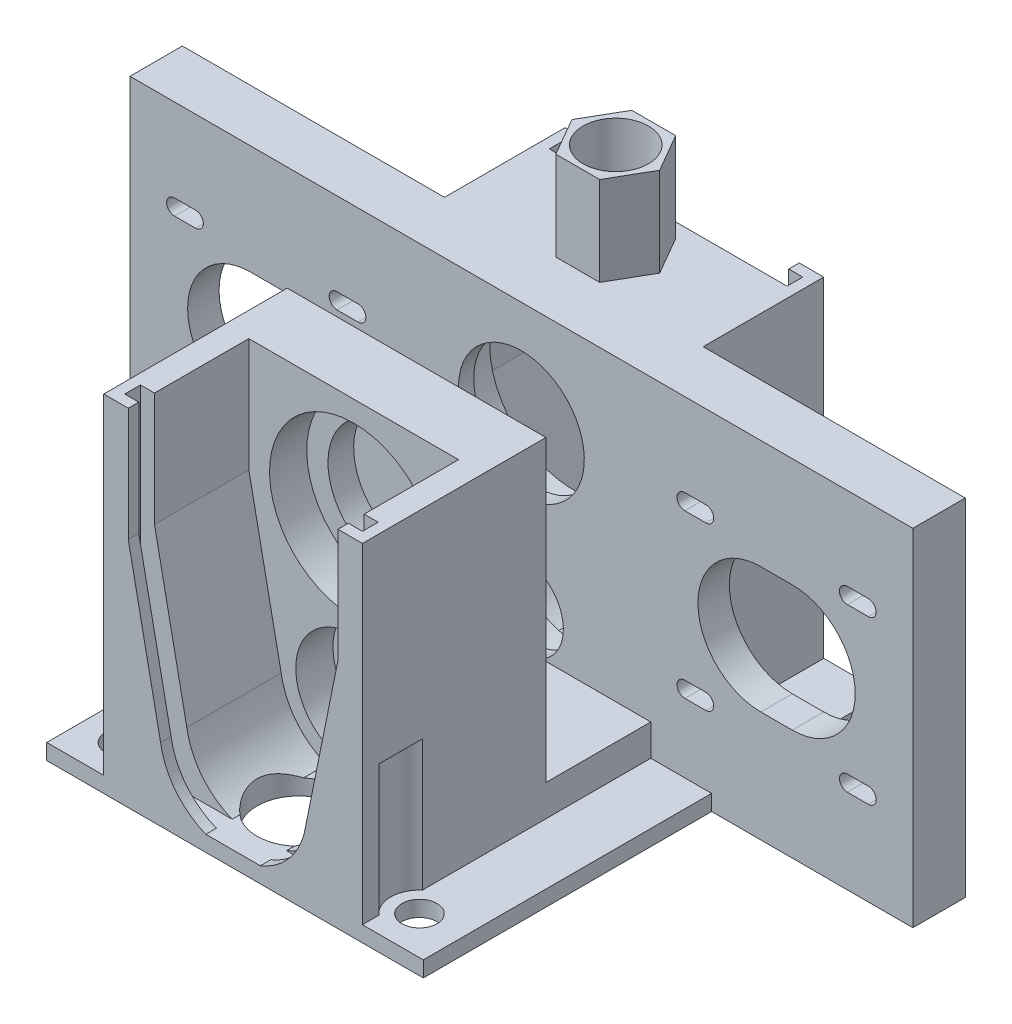
SolidWorks part; units mm, degrees
ref_plane "Front Plane" through (0, 0, 0) normal (0, 0, 1) x (1, 0, 0)
ref_plane "Top Plane" through (0, 0, 0) normal (0, 1, 0) x (1, 0, 0)
ref_plane "Right Plane" through (0, 0, 0) normal (1, 0, 0) x (0, 0, -1)
ref_axis "Axis1" through (88.99, 0, 0) along (-1, 0, 0)
ref_plane "Plane1" through (0, 0, 0) normal (0, 0, -1) x (-1, 0, 0)
ref_plane "Plane2" through (0, 0, 0) normal (0, -1, 0) x (-1, 0, 0)
ref_plane "Plane3" through (0, 0, -42) normal (0, 0, -1) x (-1, 0, 0)
sketch "Sketch2" plane through (0, 0, 0) normal (0, 0, -1) x (-1, 0, 0)
  line L2 (0, 58.0413) -> (0, 28.0413) construction
  line L3 (-24.6785, 78.0413) -> (24.6785, 78.0413)
  line L4 (57.5751, 12.0413) -> (-72.0682, 12.0413) construction
  line L5 (-24.6785, 78.0413) -> (-24.6785, 12.0413)
  line L6 (-24.6785, 12.0413) -> (24.6785, 12.0413)
  line L7 (24.6785, 12.0413) -> (24.6785, 78.0413)
  circle A0 centre (0, 28.0413) radius 11 construction
  circle A1 centre (0, 58.0413) radius 16 construction
  point P4 (0, 58.0413)
  point P6 (0, 28.0413)
  point P7 (20.0824, 64.1811)
  point P8 (15.3009, 32.7193)
  dimension "D1" = 32
  dimension "D2" = 22
  dimension "D6" = 66
  dimension "D3" = 30
  dimension "D5" = 20
  dimension "D4" = 16
extrude "Boss-Extrude1" add sketch "Sketch2" along normal blind 65
ref_plane "Plane5" through (0, 12.0413, 0) normal (0, -1, 0) x (-1, 0, 0)
sketch "Sketch3" plane through (0, 0, 0) normal (0, 0, -1) x (-1, 0, 0)
  line L0 (-24.6785, 12.0413) -> (24.6785, 12.0413) construction
  line L1 (0, 0) -> (0, 102.6324) construction
  circle A0 centre (0, 28.0413) radius 8
  circle A1 centre (0, 58.0413) radius 12
  circle A3 centre (0, 58.0413) radius 16 construction
  circle A4 centre (0, 28.0413) radius 11 construction
  dimension "D1" = 4
  dimension "D2" = 3
  dimension "D4" = 16
  dimension "D5" = 22
  dimension "D6" = 32
  dimension "D3" = 30
extrude "Cut-Extrude1" cut sketch "Sketch3" along normal blind 42
sketch "Sketch5" plane through (0, 0, -42) normal (0, 0, -1) x (-1, 0, 0)
  line L2 (-20, 76.0413) -> (20, 76.0413)
  line L4 (-24.6785, 12.0413) -> (24.6785, 12.0413) construction
  line L6 (13.8042, 25.708) -> (20, 49.5058)
  line L7 (-20, 49.5726) -> (-13.8042, 25.708)
  line L10 (24.6785, 78.0413) -> (-24.6785, 78.0413) construction
  line L11 (-20, 76.0413) -> (-20, 49.5726)
  line L12 (20, 76.0413) -> (20, 49.5058)
  circle A1 centre (0, 58.0413) radius 16 construction
  arc A3 (-13.8042, 25.708) -> (13.8042, 25.708) centre (0, 28.0413) ccw
  point P0 (0, 0)
  dimension "D2" = 16
  dimension "D1" = 14
  dimension "D6" = 32
  dimension "D5" = 2
  dimension "D7" = 30
  dimension "D8" = 20
  dimension "D9" = 20
extrude "Cut-Extrude2" cut sketch "Sketch5" along normal through all
sketch "Sketch6" plane through (0, 0, 0) normal (0, 0, -1) x (-1, 0, 0)
  circle A0 centre (0, 58.0413) radius 16.05
  circle A1 centre (0, 58.0413) radius 12 construction
  circle A2 centre (0, 28.0413) radius 11.05
  circle A3 centre (0, 28.0413) radius 8 construction
  dimension "D1" = 32.1
  dimension "D2" = 22.1
extrude "Cut-Extrude3" cut sketch "Sketch6" along normal blind 7.1
sketch "Sketch7" plane through (0, 0, -42) normal (0, 0, -1) x (-1, 0, 0)
  circle A2 centre (0, 58.0413) radius 16.05
  circle A3 centre (0, 58.0413) radius 16.05
  circle A5 centre (0, 28.0413) radius 11.05
  circle A6 centre (0, 28.0413) radius 11.05
  dimension "D1" = 0
  dimension "D2" = 0
extrude "Cut-Extrude4" cut sketch "Sketch7" against normal blind 7.1
sketch "Sketch8" plane through (0, 0, 0) normal (0, 0, -1) x (-1, 0, 0)
  line L2 (24.6785, 78.0413) -> (-24.6785, 78.0413)
  line L3 (24.6785, 78.0413) -> (24.6785, 12.0413)
  line L4 (24.6785, 12.0413) -> (-24.6785, 12.0413)
  line L5 (-24.6785, 12.0413) -> (-24.6785, 78.0413)
extrude "Boss-Extrude2" add sketch "Sketch8" against normal blind 23
sketch "Sketch9" plane through (0, 0, 0) normal (0, 0, -1) x (-1, 0, 0)
  line L2 (20, 78.0413) -> (-20, 78.0413)
  line L4 (-24.6785, 12.0413) -> (24.6785, 12.0413) construction
  line L5 (20, 78.0413) -> (20, 56.3516)
  line L6 (-20, 56.3516) -> (-13.8326, 25.8825)
  line L7 (13.8326, 25.8825) -> (20, 56.3516)
  line L8 (-20, 78.0413) -> (-20, 56.3516)
  circle A0 centre (0, 56.2822) radius 16 construction
  arc A3 (-13.8326, 25.8825) -> (13.8326, 25.8825) centre (0, 28.0413) ccw
  point P20 (-4.1122, 64.6997)
  dimension "D1" = 14
  dimension "D5" = 32
  dimension "D2" = 16
  dimension "D6" = 20
  dimension "D7" = 20
extrude "Cut-Extrude5" cut sketch "Sketch9" against normal through all
ref_plane "Plane4" through (0, 0, -32) normal (0, 0, -1) x (-1, 0, 0)
sketch "Sketch10" plane through (0, 0, -32) normal (0, 0, -1) x (-1, 0, 0)
  line L1 (32.0175, 70.0413) -> (32.0175, 29.2185)
  line L2 (-24.6785, 12.0413) -> (24.6785, 12.0413) construction
  line L5 (-28.9461, 62.8412) -> (-28.9461, 21.0413)
  line L8 (0.9045, 21.0413) -> (-28.9461, 21.0413)
  line L9 (0, 0) -> (0, 85.4363) construction
  line L10 (0.9045, 21.0413) -> (32.0175, 29.2185)
  line L12 (-28.9461, 62.8412) -> (-28.9461, 84.6224)
  line L13 (-28.9461, 84.6224) -> (32.0175, 84.6224)
  line L14 (32.0175, 84.6224) -> (32.0175, 70.0413)
  circle A0 centre (0, 58.0413) radius 10 construction
  circle A1 centre (0, 58.0413) radius 16 construction
  circle A2 centre (0, 28.0413) radius 11 construction
  circle A4 centre (0, 28.0413) radius 4 construction
  dimension "D1" = 32
  dimension "D2" = 22
  dimension "D3" = 30
  dimension "D4" = 20
  dimension "D5" = 8
  dimension "D6" = 16
  dimension "D7" = 7
  dimension "D10" = 7
extrude "Cut-Extrude6" cut sketch "Sketch10" against normal blind 20
sketch "Sketch12" plane through (0, 0, 0) normal (0, 1, 0) x (1, 0, 0)
  circle A0 centre (0, -10.444) radius 8
  ellipse E0 centre (0, -2.444) end of major axis (14, -2.444) minor radius 1.2202 (13.8326, -2.2558) -> (-13.8326, -2.2558) ccw construction
  dimension "D1" = 16
  dimension "D2" = 8
extrude "Cut-Extrude8" cut sketch "Sketch12" along normal up to surface (14.0413 mm away) up to face at (0, 19.9619, 11.5)
sketch "Sketch13" plane through (0, 12.0413, 0) normal (0, -1, 0) x (-1, 0, 0)
  line L2 (24.6785, 12) -> (24.6785, 32)
  line L3 (24.6785, 12) -> (24.6785, 32) construction
  line L4 (24.6785, 32) -> (24.6785, 42)
  line L5 (-24.6785, 65) -> (24.6785, 65) construction
  line L7 (24.6785, 42) -> (74.6785, 42)
  line L8 (97.889, 42) -> (-97.889, 42) construction
  line L9 (74.6785, 42) -> (74.6785, 32)
  line L10 (97.889, 32) -> (-97.889, 32) construction
  line L11 (74.6785, 32) -> (24.6785, 32)
  line L12 (-24.6785, 42) -> (-74.6785, 42)
  line L13 (-24.6785, 65) -> (-24.6785, -23) construction
  line L14 (-74.6785, 42) -> (-74.6785, 32)
  line L15 (-74.6785, 32) -> (-24.6785, 32)
  line L16 (-24.6785, 32) -> (-24.6785, 42)
  dimension "D3" = 50
  dimension "D2" = 23
  dimension "D1" = 0
extrude "Boss-Extrude3" add sketch "Sketch13" against normal up to surface (66 mm away) up to face at (0, 78.0413, -48.5)
sketch "Sketch15" plane through (0, 0, -42) normal (0, 0, -1) x (-1, 0, 0)
  line L0 (0, 0) -> (0, 87.2744) construction
  line L1 (74.6785, 78.0413) -> (74.6785, 12.0413) construction
  line L2 (25.6785, 66.3413) -> (71.6785, 66.3413)
  line L3 (25.6785, 66.3413) -> (25.6785, 24.0413)
  line L4 (25.6785, 24.0413) -> (71.6785, 24.0413)
  line L5 (71.6785, 66.3413) -> (71.6785, 24.0413)
  line L6 (24.6785, 12.0413) -> (24.6785, 78.0413) construction
  line L7 (-27.1464, 12.0413) -> (27.1464, 12.0413) construction
  line L8 (-71.6785, 66.3413) -> (-71.6785, 24.0413)
  line L9 (-25.6785, 24.0413) -> (-71.6785, 24.0413)
  line L10 (-25.6785, 66.3413) -> (-25.6785, 24.0413)
  line L11 (-25.6785, 66.3413) -> (-71.6785, 66.3413)
  dimension "D1" = 3
  dimension "D2" = 1
  dimension "D3" = 42.3
  dimension "D4" = 12
extrude "Cut-Extrude9" cut sketch "Sketch15" against normal blind 4
sketch "Sketch16" plane through (0, 0, -42) normal (0, 0, -1) x (-1, 0, 0)
  line L0 (-105.1978, 45.1913) -> (88.1587, 45.1913) construction
  line L1 (71.6785, 66.3413) -> (25.6785, 66.3413) construction
  line L2 (25.6785, 24.0413) -> (71.6785, 24.0413) construction
  line L3 (45.6785, 45.1913) -> (51.6785, 45.1913) construction
  line L4 (45.6785, 57.1913) -> (51.6785, 57.1913)
  line L5 (45.6785, 33.1913) -> (51.6785, 33.1913)
  line L6 (48.6785, 83.554) -> (48.6785, 16.5047) construction
  line L7 (25.6785, 66.3413) -> (25.6785, 24.0413) construction
  line L8 (71.6785, 24.0413) -> (71.6785, 66.3413) construction
  line L9 (31.1785, 60.6913) -> (35.1785, 60.6913) construction
  line L10 (31.1785, 62.1913) -> (35.1785, 62.1913)
  line L11 (31.1785, 59.1913) -> (35.1785, 59.1913)
  line L12 (66.1785, 60.6913) -> (62.1785, 60.6913) construction
  line L25 (66.1785, 62.1913) -> (62.1785, 62.1913)
  line L26 (66.1785, 59.1913) -> (62.1785, 59.1913)
  line L27 (31.1785, 29.6913) -> (35.1785, 29.6913) construction
  line L28 (31.1785, 28.1913) -> (35.1785, 28.1913)
  line L29 (31.1785, 31.1913) -> (35.1785, 31.1913)
  line L30 (66.1785, 29.6913) -> (62.1785, 29.6913) construction
  line L31 (66.1785, 28.1913) -> (62.1785, 28.1913)
  line L32 (66.1785, 31.1913) -> (62.1785, 31.1913)
  line L33 (0, 0) -> (0, 89.9864) construction
  line L34 (-45.6785, 45.1913) -> (-51.6785, 45.1913) construction
  line L35 (-45.6785, 57.1913) -> (-51.6785, 57.1913)
  line L36 (-45.6785, 33.1913) -> (-51.6785, 33.1913)
  line L37 (-31.1785, 60.6913) -> (-35.1785, 60.6913) construction
  line L38 (-31.1785, 62.1913) -> (-35.1785, 62.1913)
  line L39 (-31.1785, 59.1913) -> (-35.1785, 59.1913)
  line L40 (-66.1785, 60.6913) -> (-62.1785, 60.6913) construction
  line L41 (-66.1785, 62.1913) -> (-62.1785, 62.1913)
  line L42 (-66.1785, 59.1913) -> (-62.1785, 59.1913)
  line L43 (-31.1785, 29.6913) -> (-35.1785, 29.6913) construction
  line L44 (-31.1785, 28.1913) -> (-35.1785, 28.1913)
  line L45 (-31.1785, 31.1913) -> (-35.1785, 31.1913)
  line L46 (-66.1785, 29.6913) -> (-62.1785, 29.6913) construction
  line L47 (-66.1785, 28.1913) -> (-62.1785, 28.1913)
  line L48 (-66.1785, 31.1913) -> (-62.1785, 31.1913)
  arc A0 (45.6785, 57.1913) -> (45.6785, 33.1913) centre (45.6785, 45.1913) ccw
  arc A1 (51.6785, 33.1913) -> (51.6785, 57.1913) centre (51.6785, 45.1913) ccw
  arc A2 (31.1785, 62.1913) -> (31.1785, 59.1913) centre (31.1785, 60.6913) ccw
  arc A3 (35.1785, 59.1913) -> (35.1785, 62.1913) centre (35.1785, 60.6913) ccw
  arc A16 (66.1785, 62.1913) -> (66.1785, 59.1913) centre (66.1785, 60.6913) cw
  arc A17 (62.1785, 59.1913) -> (62.1785, 62.1913) centre (62.1785, 60.6913) cw
  arc A18 (31.1785, 28.1913) -> (31.1785, 31.1913) centre (31.1785, 29.6913) cw
  arc A19 (35.1785, 31.1913) -> (35.1785, 28.1913) centre (35.1785, 29.6913) cw
  arc A20 (66.1785, 28.1913) -> (66.1785, 31.1913) centre (66.1785, 29.6913) ccw
  arc A21 (62.1785, 31.1913) -> (62.1785, 28.1913) centre (62.1785, 29.6913) ccw
  arc A22 (-45.6785, 57.1913) -> (-45.6785, 33.1913) centre (-45.6785, 45.1913) cw
  arc A23 (-51.6785, 33.1913) -> (-51.6785, 57.1913) centre (-51.6785, 45.1913) cw
  arc A24 (-31.1785, 62.1913) -> (-31.1785, 59.1913) centre (-31.1785, 60.6913) cw
  arc A25 (-35.1785, 59.1913) -> (-35.1785, 62.1913) centre (-35.1785, 60.6913) cw
  arc A26 (-66.1785, 62.1913) -> (-66.1785, 59.1913) centre (-66.1785, 60.6913) ccw
  arc A27 (-62.1785, 59.1913) -> (-62.1785, 62.1913) centre (-62.1785, 60.6913) ccw
  arc A28 (-31.1785, 28.1913) -> (-31.1785, 31.1913) centre (-31.1785, 29.6913) ccw
  arc A29 (-35.1785, 31.1913) -> (-35.1785, 28.1913) centre (-35.1785, 29.6913) ccw
  arc A30 (-66.1785, 28.1913) -> (-66.1785, 31.1913) centre (-66.1785, 29.6913) cw
  arc A31 (-62.1785, 31.1913) -> (-62.1785, 28.1913) centre (-62.1785, 29.6913) cw
  point P8 (48.6785, 45.1913)
  point P14 (33.1785, 60.6913)
  point P28 (64.1785, 60.6913)
  point P36 (33.1785, 29.6913)
  point P43 (64.1785, 29.6913)
  point P52 (-48.6785, 45.1913)
  point P59 (-33.1785, 60.6913)
  point P66 (-64.1785, 60.6913)
  point P73 (-33.1785, 29.6913)
  point P80 (-64.1785, 29.6913)
  dimension "D1" = 12
  dimension "D3" = 31
  dimension "D4" = 1.5
  dimension "D2" = 31
  dimension "D5" = 4
  dimension "D6" = 6
extrude "Cut-Extrude10" cut sketch "Sketch16" against normal up to next
sketch "Sketch17" plane through (0, 78.0413, 0) normal (0, 1, 0) x (1, 0, 0)
  line L0 (0, 55.3583) -> (0, 85.749) construction
  line L1 (-35.5458, 50) -> (45.8299, 50) construction
  line L4 (97.889, 42) -> (-97.889, 42) construction
  line L5 (8.3716, 50) -> (4.1858, 57.25)
  line L6 (4.1858, 57.25) -> (-4.1858, 57.25)
  line L7 (-4.1858, 57.25) -> (-8.3716, 50)
  line L8 (-8.3716, 50) -> (-4.1858, 42.75)
  line L9 (-4.1858, 42.75) -> (4.1858, 42.75)
  line L10 (4.1858, 42.75) -> (8.3716, 50)
  circle A0 centre (0, 50) radius 7.25 construction
  circle A1 centre (0, 50) radius 6.25
  dimension "D2" = 12.5
  dimension "D1" = 14.5
  dimension "D3" = 8
extrude "Boss-Extrude4" add sketch "Sketch17" along normal blind 17
sketch "Sketch18" plane through (0, 78.0413, 0) normal (0, 1, 0) x (1, 0, 0)
  circle A2 centre (0, 50) radius 6.25
  circle A3 centre (0, 50) radius 6.25
  dimension "D1" = 0
extrude "Cut-Extrude11" cut sketch "Sketch18" against normal up to next
sketch "Sketch19" plane through (0, 12.0413, 0) normal (0, -1, 0) x (-1, 0, 0)
  line L0 (-66.3049, 12.556) -> (66.3049, 12.556) construction
  line L1 (0, 76.6155) -> (0, 65) construction
  line L2 (-61.7241, 74.2802) -> (0.6987, 11.8573) construction
  line L4 (13.4481, 26.0042) -> (0, 12.556) construction
  line L7 (-36.2843, 48.8403) -> (-36.2843, -23)
  line L9 (35.556, 48.8403) -> (35.556, -23)
  line L10 (-36.2843, 48.8403) -> (-36.2843, 65)
  line L12 (35.556, 65) -> (35.556, 48.8403)
  line L27 (0, 42) -> (0, -57.588) construction
  line L28 (-25.9179, -13.3619) -> (-763.264, -750.708) construction
  line L29 (-36.2843, 65) -> (35.556, 65)
  line L30 (-36.2843, -23) -> (35.556, -23)
  circle A3 centre (-28.2843, 40.8403) radius 3.3465
  circle A6 centre (28.2843, 40.8403) radius 3.3465
  circle A7 centre (-28.2843, -15.7282) radius 3.3465
  circle A8 centre (28.2843, -15.7282) radius 3.3465
  circle A10 centre (0, -10.444) radius 8
  circle A11 centre (0, -10.444) radius 8
  point P3 (0, 12.556)
  dimension "D2" = 45
  dimension "D1" = 45
  dimension "D5" = 40
  dimension "D6" = 8
  dimension "D3" = 0
extrude "Boss-Extrude5" add sketch "Sketch19" against normal blind 3
sketch "Sketch20" plane through (0, 15.0413, 0) normal (0, 1, 0) x (1, 0, 0)
  circle A0 centre (-28.2843, -15.7282) radius 5.5
  circle A1 centre (28.2843, -15.7282) radius 5.5
  circle A2 centre (28.2843, 40.8403) radius 5.5
  circle A3 centre (-28.2843, 40.8403) radius 5.5
  dimension "D1" = 11
extrude "Cut-Extrude12" cut sketch "Sketch20" along normal blind 25
sketch "Sketch21" plane through (0, 12.0413, 0) normal (0, -1, 0) x (-1, 0, 0)
  circle A0 centre (-28.2843, 40.8403) radius 3.3465
  arc A1 (-25.1451, 42) -> (-31.4234, 42) centre (-28.2843, 40.8403) ccw construction
  circle A2 centre (28.2843, 40.8403) radius 3.3465
  arc A3 (31.4234, 42) -> (25.1451, 42) centre (28.2843, 40.8403) ccw construction
extrude "Cut-Extrude13" cut sketch "Sketch21" against normal up to next
sketch "Sketch22" plane through (0, 0, 0) normal (1, 0, 0) x (0, 0, -1)
  line L0 (63, 78.0413) -> (63, 15.0413)
  line L3 (65, 78.0413) -> (42, 78.0413) construction
  line L7 (44.9934, 15.0413) -> (65, 15.0413) construction
  line L8 (63, 15.0413) -> (65, 15.0413)
  line L9 (65, 78.0413) -> (65, 15.0413) construction
  line L10 (-21, 81.0679) -> (-21, 15.0413)
  line L12 (-23, 15.0413) -> (-19.8814, 15.0413) construction
  line L13 (-21, 15.0413) -> (-23, 15.0413)
  line L14 (-23, 78.0413) -> (-23, 15.0413) construction
  dimension "D1" = 2
  dimension "D2" = 2
sketch "Sketch23" plane through (0, 78.0413, 0) normal (0, 1, 0) x (1, 0, 0)
  line L0 (-24.6785, 65) -> (24.6785, 65) construction
  line L1 (-22.6785, 63) -> (22.6785, 63)
  line L2 (-22.6785, 63) -> (-22.6785, 60)
  line L3 (-22.6785, 60) -> (22.6785, 60)
  line L4 (22.6785, 63) -> (22.6785, 60)
  line L5 (-24.6785, 65) -> (-24.6785, 44.9934) construction
  line L6 (24.6785, 44.9934) -> (24.6785, 65) construction
  line L8 (-22.6785, -18) -> (22.6785, -18)
  line L9 (-22.6785, -18) -> (-22.6785, -21)
  line L10 (-22.6785, -21) -> (22.6785, -21)
  line L11 (22.6785, -18) -> (22.6785, -21)
  line L12 (-24.6785, 12) -> (-24.6785, -23) construction
  line L13 (24.6785, 12) -> (24.6785, -23) construction
  line L14 (5.1962, -23) -> (-5.1962, -23) construction
  dimension "D1" = 2
  dimension "D2" = 2
  dimension "D3" = 2
  dimension "D4" = 3
  dimension "D5" = 2
  dimension "D6" = 3
  dimension "D7" = 2
  dimension "D8" = 2
extrude "Cut-Extrude14" cut sketch "Sketch23" against normal up to surface (63 mm away) up to face at (-27.9886, 15.0413, 2.2427)
sketch "Sketch24" plane through (0, 0, -65) normal (0, 0, -1) x (-1, 0, 0)
  line L0 (24.6785, 78.0413) -> (-24.6785, 78.0413) construction
  line L1 (-20, 76.0413) -> (20, 76.0413)
  line L2 (-20, 76.0413) -> (-20, 78.0413)
  line L3 (-20, 78.0413) -> (20, 78.0413)
  line L4 (20, 76.0413) -> (20, 78.0413)
extrude "Cut-Extrude15" cut sketch "Sketch24" against normal up to next
